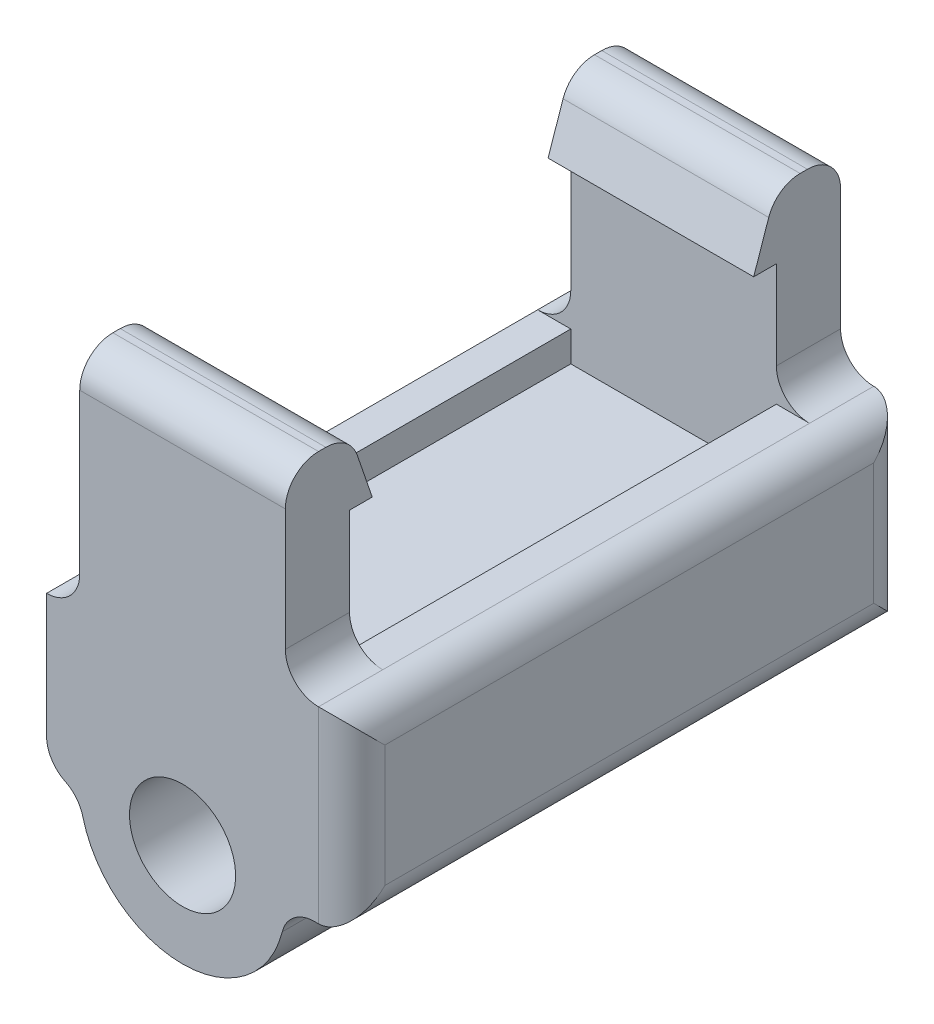
SolidWorks part; units mm, degrees
material "ABS"
ref_plane "Plano frontal" through (0, 0, 0) normal (0, 0, 1) x (1, 0, 0)
ref_plane "Plano superior" through (0, 0, 0) normal (0, 1, 0) x (1, 0, 0)
ref_plane "Plano direito" through (0, 0, 0) normal (1, 0, 0) x (0, 0, -1)
sketch "Esboço1" plane through (0, 0, 0) normal (0, 0, 1) x (1, 0, 0)
  circle A0 centre (16.0167, 16.0167) radius 3.1
  circle A1 centre (16.0167, 16.0167) radius 1.55
  dimension "D1" = 3.1
extrude "Ressalto-extrusão1" add sketch "Esboço1" along normal up to vertex (16.74 mm away)
sketch "Sketch1" plane through (0, 0, 0) normal (0, 0, -1) x (-1, 0, 0)
  line L2 (-12.9167, 16.0167) -> (-12.9167, 19.6347)
  line L3 (-12.9167, 19.6347) -> (-19.1167, 19.6347)
  line L4 (-19.1167, 16.0167) -> (-19.1167, 19.6347)
  circle A0 centre (-16.0167, 16.0167) radius 3.1 construction
  arc A1 (-12.9167, 16.0167) -> (-19.1167, 16.0167) centre (-16.0167, 16.0167) ccw
extrude "Boss-Extrude1" add sketch "Sketch1" against normal up to surface (16.74 mm away) up to face at (19.1167, 16.0167, 16.74)
sketch "Sketch2" plane through (0, 19.6347, 0) normal (0, 1, 0) x (1, 0, 0)
  line L0 (19.1167, -16.74) -> (19.1167, 0) construction
  line L1 (12.9167, 0) -> (19.1167, 0)
  line L2 (12.9167, 0) -> (12.9167, -1.935)
  line L3 (12.9167, -1.935) -> (19.1167, -1.935)
  line L4 (19.1167, 0) -> (19.1167, -1.935)
  line L6 (19.1167, -14.805) -> (12.9167, -14.805)
  line L7 (19.1167, -14.805) -> (19.1167, -16.74)
  line L8 (19.1167, -16.74) -> (12.9167, -16.74)
  line L9 (12.9167, -14.805) -> (12.9167, -16.74)
  dimension "D1" = 1.935
  dimension "D2" = 1.935
  dimension "D3" = 16.74
extrude "Boss-Extrude2" add sketch "Sketch2" along normal offset from surface (7.715 mm away) 2
sketch "Sketch4" plane through (12.9167, 0, 0) normal (-1, 0, 0) x (0, 0, 1)
  line L0 (1.935, 27.3497) -> (1.935, 25.3497)
  line L1 (1.935, 25.3497) -> (2.6193, 25.3497)
  line L2 (2.6193, 25.3497) -> (1.935, 27.3497)
  line L3 (8.37, 25.3497) -> (8.37, 25.0062) construction
  line L4 (14.1207, 25.3497) -> (14.805, 27.3497)
  line L5 (14.805, 25.3497) -> (14.1207, 25.3497)
  line L6 (14.805, 27.3497) -> (14.805, 25.3497)
  line L7 (1.935, 27.3497) -> (1.935, 19.6347) construction
extrude "Boss-Extrude3" add sketch "Sketch4" against normal up to surface (6.2 mm away) up to face at (19.1167, 23.0699, 9.1744)
sketch "Sketch5" plane through (19.1167, 0, 0) normal (1, 0, 0) x (0, 0, -1)
  line L0 (-16.74, 16.0167) -> (0, 16.0167) construction
  line L1 (-16.74, 16.0167) -> (0, 16.0167)
  line L2 (-16.74, 16.0167) -> (-16.74, 21.6832)
  line L3 (-16.74, 21.6832) -> (0, 21.6832)
  line L4 (0, 16.0167) -> (0, 21.6832)
  line L5 (-16.74, 16.0167) -> (-16.74, 12.9167) construction
  line L6 (0, 27.3497) -> (0, 16.0167) construction
extrude "Boss-Extrude4" add sketch "Sketch5" along normal blind 2
sketch "Sketch6" plane through (12.9167, 0, 0) normal (-1, 0, 0) x (0, 0, 1)
  line L0 (0, 16.0167) -> (0, 12.9167) construction
  line L1 (0, 16.0167) -> (16.74, 16.0167)
  line L2 (0, 16.0167) -> (0, 20.5461)
  line L3 (0, 20.5461) -> (16.74, 20.5461)
  line L4 (16.74, 16.0167) -> (16.74, 20.5461)
  line L5 (0, 16.0167) -> (0, 27.3497) construction
  line L6 (16.74, 16.0167) -> (16.74, 27.3497) construction
extrude "Boss-Extrude5" add sketch "Sketch6" along normal blind 1
fillet "Fillet1" radius 1 14 edges at (21.1167, 21.6832, 8.37) (21.1167, 18.8499, 0) (21.1167, 16.0167, 8.37) (21.1167, 18.8499, 16.74) (16.0167, 27.3497, 0) (16.0167, 27.3497, 1.935) (16.0167, 27.3497, 16.74) (16.0167, 27.3497, 14.805) (19.1167, 21.6832, 15.7725) (12.9167, 20.5461, 15.7725) (12.9167, 20.5461, 0.9675) (19.1167, 21.6832, 0.9675) (12.9167, 16.0167, 8.37) (19.1167, 16.0167, 8.37)
fillet "Fillet4" radius 1 1 edges at (11.9167, 16.0167, 8.37)
hole_wizard "M3 Clearance Hole1" positions "Sketch8" profile "Sketch7" hole size "M3" standard "ISO" end condition through all
sketch "Sketch8" plane through (0, 0, 0) normal (0, 0, -1) x (-1, 0, 0)
  point P0 (-16.0167, 16.0167)
sketch "Sketch7" plane through (16.0167, 16.0167, 0) normal (1, 0, 0) x (0, 1, 0)
  line L0 (0, 0) -> (0, 16.74)
  line L1 (0, 16.74) -> (1.6, 16.74)
  line L2 (1.6, 16.74) -> (1.6, 0)
  line L5 (1.6, 0) -> (0, 0)
  line L11 (0, -6.35) -> (0, 107.95) construction
  dimension "Thru Hole Dia." = 3.2
  dimension "Thru Hole Depth" = 16.74
equation "\"D2@Sketch2\"=(\"D3@Sketch2\"-12.87)/2"
equation "\"D1@Sketch2\"=\"D2@Sketch2\""
